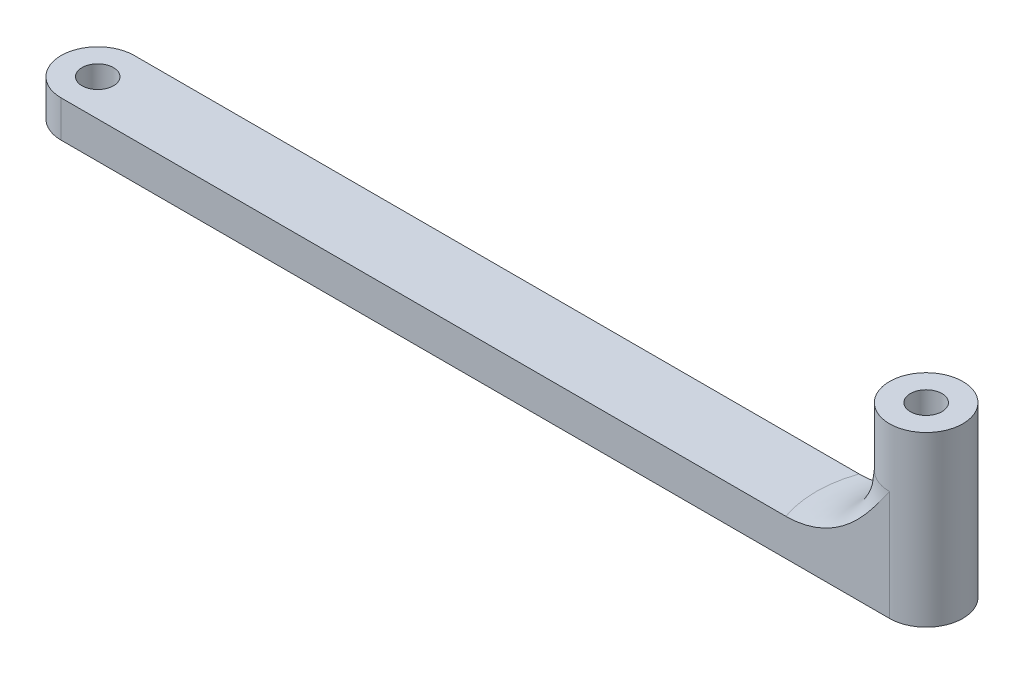
SolidWorks part; units mm, degrees
ref_plane "Front Plane" through (0, 0, 0) normal (0, 0, 1) x (1, 0, 0)
ref_plane "Top Plane" through (0, 0, 0) normal (0, 1, 0) x (1, 0, 0)
ref_plane "Right Plane" through (0, 0, 0) normal (1, 0, 0) x (0, 0, -1)
sketch "Sketch1" plane through (0, 0, 0) normal (0, 1, 0) x (1, 0, 0)
  line L0 (0, 0) -> (-113, 0) construction
  line L1 (-113, 0) -> (-113, 5) construction
  line L2 (-113, 0) -> (-113, -5) construction
  line L3 (0, 0) -> (0, -5) construction
  line L4 (0, 0) -> (0, 5) construction
  line L5 (-113, 5) -> (0, 5)
  line L6 (0, -5) -> (-113, -5)
  arc A0 (-113, 5) -> (-113, -5) centre (-113, 0) ccw
  arc A1 (0, 5) -> (0, -5) centre (0, 0) cw
  dimension "D1" = 113
  dimension "D2" = 5
  dimension "D3" = 5
  dimension "D4" = 5
  dimension "D5" = 5
extrude "Boss-Extrude1" add sketch "Sketch1" along normal blind 5
sketch "Sketch2" plane through (0, 0, 0) normal (0, 1, 0) x (1, 0, 0)
  circle A0 centre (0, 0) radius 5
extrude "Boss-Extrude2" add sketch "Sketch2" along normal blind 23
fillet "Fillet1" radius 10 1 edges at (-5, 5, 0)
sketch "Sketch3" plane through (0, 0, 0) normal (0, 1, 0) x (1, 0, 0)
  circle A0 centre (-113, 0) radius 2.15
  circle A1 centre (0, 0) radius 2.15
  dimension "D1" = 4.3
  dimension "D2" = 4.3
extrude "Cut-Extrude1" cut sketch "Sketch3" along normal blind 30
